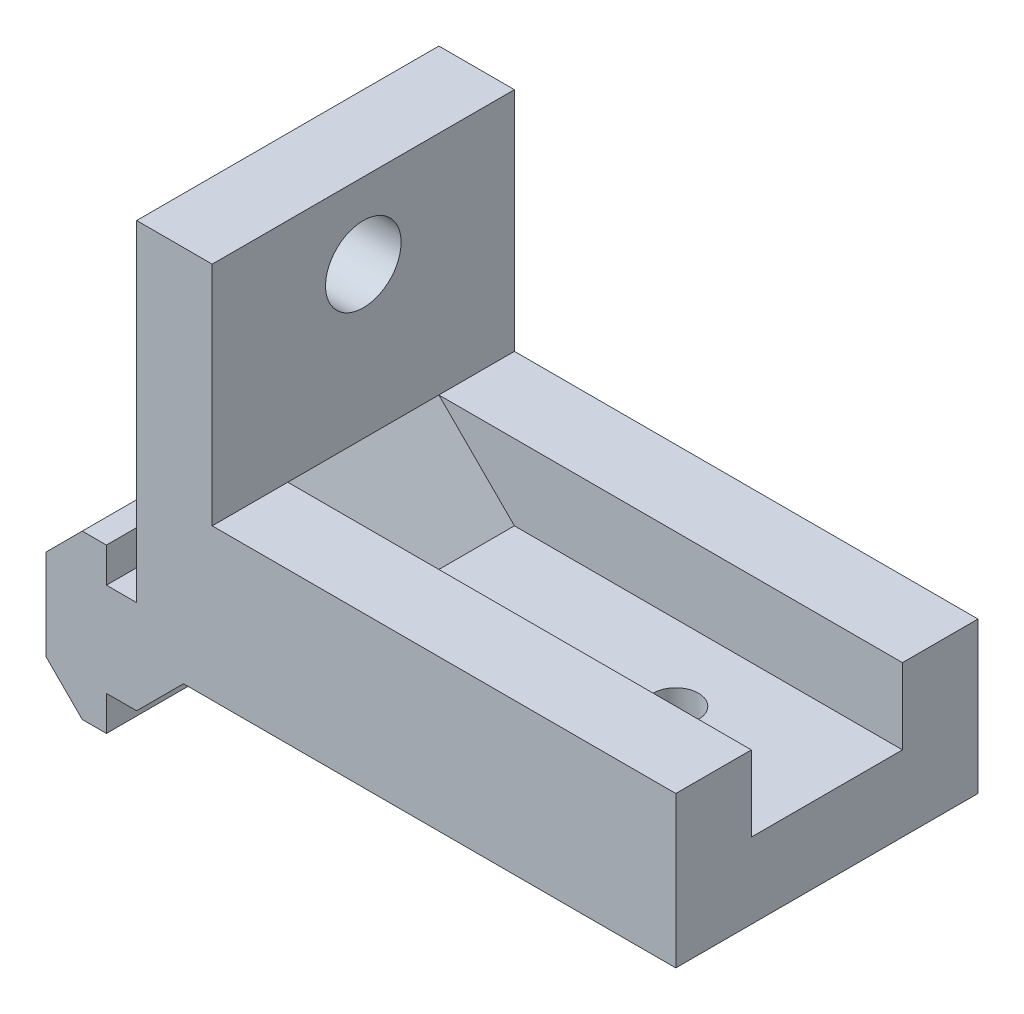
SolidWorks part; units mm, degrees
ref_plane "前视基准面" through (0, 0, 0) normal (0, 0, 1) x (1, 0, 0)
ref_plane "上视基准面" through (0, 0, 0) normal (0, 1, 0) x (1, 0, 0)
ref_plane "右视基准面" through (0, 0, 0) normal (1, 0, 0) x (0, 0, -1)
sketch "草图1" plane through (0, 0, 0) normal (0, 1, 0) x (1, 0, 0)
  line L0 (35.68, 5) -> (25.68, 5)
  line L1 (35.68, 10) -> (0, 10)
  line L2 (35.68, 10) -> (35.68, -10)
  line L3 (35.68, -10) -> (0, -10)
  line L4 (0, 10) -> (0, -10)
  line L5 (35.68, -5) -> (25.68, -5)
  line L6 (5, 10) -> (5, -10)
  line L7 (25.68, -5) -> (5, -5)
  line L8 (25.68, 5) -> (5, 5)
  line L10 (28.8554, 0) -> (27.2677, 2.75)
  line L11 (27.2677, 2.75) -> (24.0923, 2.75)
  line L12 (24.0923, 2.75) -> (22.5046, 0)
  line L13 (22.5046, 0) -> (24.0923, -2.75)
  line L14 (24.0923, -2.75) -> (27.2677, -2.75)
  line L15 (27.2677, -2.75) -> (28.8554, 0)
  arc A0 (25.68, 5) -> (25.68, -5) centre (25.68, 0) ccw
  circle A1 centre (25.68, 0) radius 1.5
  circle A2 centre (25.68, 0) radius 2.75 construction
  point P4 (35.68, 0)
  point P12 (0, 0)
  dimension "D2" = 10
  dimension "D6" = 3
  dimension "D1" = 20
  dimension "D3" = 10
  dimension "D4" = 25.68
  dimension "D5" = 5
  dimension "D7" = 5.5
extrude "凸台-拉伸1" add sketch "草图1" along normal blind 5 contours L0 A0 L5 L2 | A0 L8 L6 L7 | L8 L0 L2 L1 L6 | L6 L1 L4 L3 | L5 L7 L6 L3 L2 | L14 L15 L10 L11 L12 L13 A1 region at (29.3649, 0, 0) region at (20.34, 0, -7.5) region at (13.4137, 0, 0) region at (20.34, 0, 7.5) region at (2.5, 0, 0) region at (27.9888, 0, 1.333)
extrude "凸台-拉伸2" add sketch "草图1<4>" along normal blind 10 contours L8 L0 L2 L1 L6 | L5 L7 L6 L3 L2 region at (20.34, 0, -7.5) region at (20.34, 0, 7.5)
sketch "草图1<4>" plane through (0, 0, 0) normal (0, 1, 0) x (1, 0, 0) same geometry as "草图1"
extrude "切除-拉伸1" cut sketch "草图1<5>" along normal blind 1.5 contours L14 L15 L10 L11 L12 L13 A1 region at (27.9888, 0, 1.333)
sketch "草图1<5>" plane through (0, 0, 0) normal (0, 1, 0) x (1, 0, 0) same geometry as "草图1"
extrude "凸台-拉伸4" add sketch "草图1<6>" along normal blind 25 contours L6 L1 L4 L3 region at (2.5, 0, 0)
sketch "草图1<6>" plane through (0, 0, 0) normal (0, 1, 0) x (1, 0, 0) same geometry as "草图1"
sketch "草图3" plane through (0, 0, 0) normal (1, 0, 0) x (0, 0, -1)
  circle A0 centre (0, 20) radius 2.5
  dimension "D1" = 5
  dimension "D2" = 20
extrude "切除-拉伸3" cut sketch "草图3" along normal up to next
sketch "草图2" plane through (0, 0, 0) normal (0, 0, 1) x (1, 0, 0)
  line L1 (0, 25) -> (0, 0) construction
  line L4 (0, 3.1) -> (-2, 3.1)
  line L5 (-2, 3.1) -> (-2, 5.4)
  line L6 (-2, 5.4) -> (-3.6, 5.4)
  line L7 (-3.6, 5.4) -> (-6, 3)
  line L8 (-6, 3) -> (-6, -3)
  line L9 (-6, -3) -> (-3.6, -5.4)
  line L10 (-3.6, -5.4) -> (-2, -5.4)
  line L11 (-2, -5.4) -> (-2, -3.1)
  line L12 (-2, -3.1) -> (0, -3.1)
  line L16 (0, -3.1) -> (0, 3.1)
  line L17 (-3.6, 5.4) -> (-3.6, -5.4) construction
  point P0 (0, 0)
  dimension "D1" = 10.8
  dimension "D2" = 2
  dimension "D3" = 4
  dimension "D4" = 6.2
  dimension "D5" = 6
extrude "凸台-拉伸3" add sketch "草图2" along normal up to surface (10 mm away) and the other way up to surface (10 mm away) up to face at (13.56, 11.6667, 10) other way up to face at (13.56, 11.6667, -10)
chamfer "倒角1" distance 3.1 angle 45 1 edges at (0, 0, 0)
chamfer "倒角2" distance 5 angle 45 1 edges at (5, 5, 0)
